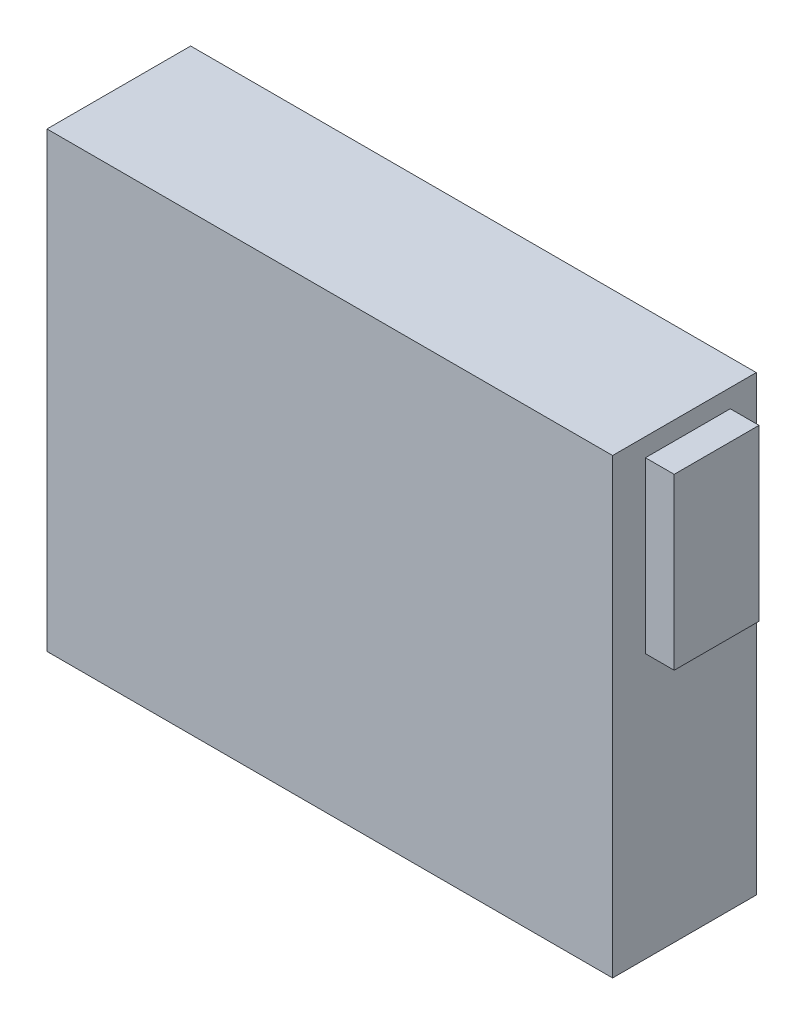
SolidWorks part; units mm, degrees
ref_plane "Front Plane" through (0, 0, 0) normal (0, 0, 1) x (1, 0, 0)
ref_plane "Top Plane" through (0, 0, 0) normal (0, 1, 0) x (1, 0, 0)
ref_plane "Right Plane" through (0, 0, 0) normal (1, 0, 0) x (0, 0, -1)
sketch "Sketch2" plane through (0, 0, 0) normal (0, 0, 1) x (1, 0, 0)
  line L1 (0, 0) -> (100, 0)
  line L2 (0, 0) -> (0, 80)
  line L3 (0, 80) -> (100, 80)
  line L4 (100, 0) -> (100, 80)
extrude "Boss-Extrude2" add sketch "Sketch2" along normal blind 25.4
sketch "Sketch3" plane through (100, 0, 0) normal (1, 0, 0) x (0, 0, -1)
  line L1 (-19.5936, 76.7554) -> (-4.5936, 76.7554)
  line L2 (-19.5936, 76.7554) -> (-19.5936, 46.7554)
  line L3 (-19.5936, 46.7554) -> (-4.5936, 46.7554)
  line L4 (-4.5936, 76.7554) -> (-4.5936, 46.7554)
extrude "Cut-Extrude1" cut sketch "Sketch3" against normal blind 10.922
sketch "Sketch4" plane through (0, 0, 0) normal (-1, 0, 0) x (0, 0, 1)
  line L1 (5.2294, 30.1831) -> (20.2294, 30.1831)
  line L2 (5.2294, 30.1831) -> (5.2294, 0.1831)
  line L3 (5.2294, 0.1831) -> (20.2294, 0.1831)
  line L4 (20.2294, 30.1831) -> (20.2294, 0.1831)
extrude "Cut-Extrude2" cut sketch "Sketch4" against normal blind 10.922
extrude "Boss-Extrude3" add sketch "Sketch3<2>" along normal blind 5.08 separate body
sketch "Sketch3<2>" plane through (100, 0, 0) normal (1, 0, 0) x (0, 0, -1) same geometry as "Sketch3"
extrude "Boss-Extrude4" add sketch "Sketch4<2>" along normal blind 5.08 separate body
sketch "Sketch4<2>" plane through (0, 0, 0) normal (-1, 0, 0) x (0, 0, 1) same geometry as "Sketch4"
